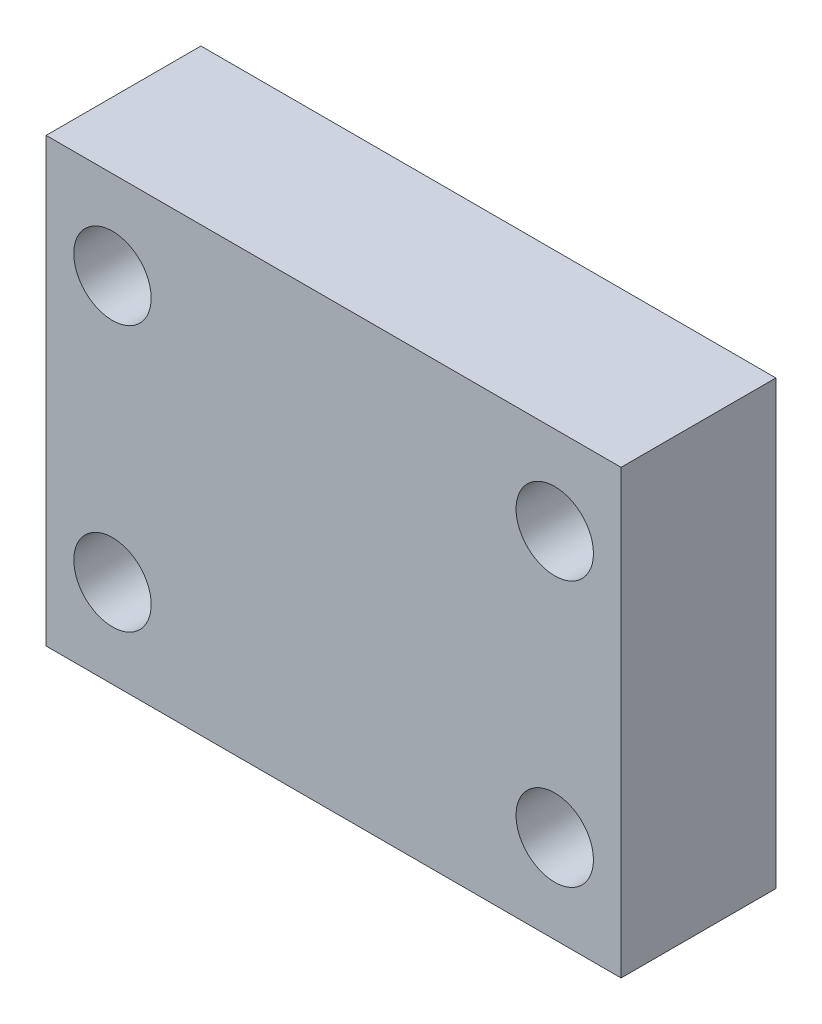
SolidWorks part; units mm, degrees
ref_plane "Front Plane" through (0, 0, 0) normal (0, 0, 1) x (1, 0, 0)
ref_plane "Top Plane" through (0, 0, 0) normal (0, 1, 0) x (1, 0, 0)
ref_plane "Right Plane" through (0, 0, 0) normal (1, 0, 0) x (0, 0, -1)
sketch "Sketch1" plane through (0, 0, 0) normal (0, 0, 1) x (1, 0, 0)
  line L1 (0, 0) -> (52, 0)
  line L2 (0, 0) -> (0, -40)
  line L3 (0, -40) -> (52, -40)
  line L4 (52, 0) -> (52, -40)
  circle A0 centre (6, -8) radius 3.5
  circle A1 centre (46, -8) radius 3.5
  circle A2 centre (6, -32) radius 3.5
  circle A3 centre (46, -32) radius 3.5
  dimension "D3" = 8
  dimension "D11" = 7
  dimension "D12" = 7
  dimension "D13" = 7
  dimension "D14" = 7
  dimension "D1" = 40
  dimension "D2" = 52
  dimension "D4" = 6
  dimension "D5" = 8
  dimension "D6" = 6
  dimension "D7" = 6
  dimension "D8" = 8
  dimension "D9" = 6
  dimension "D10" = 8
extrude "Boss-Extrude1" add sketch "Sketch1" along normal blind 14
